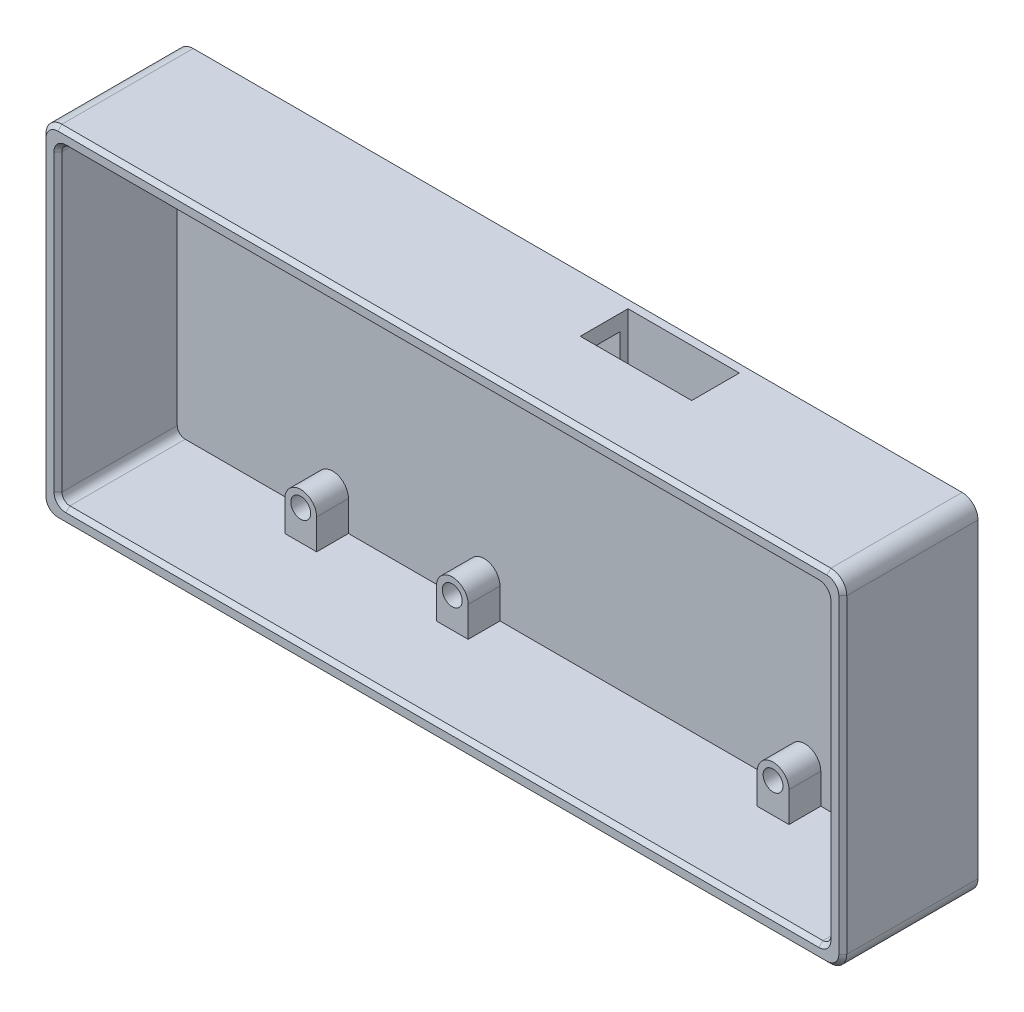
SolidWorks part; units mm, degrees
ref_plane "前视基准面" through (0, 0, 0) normal (0, 0, 1) x (1, 0, 0)
ref_plane "上视基准面" through (0, 0, 0) normal (0, 1, 0) x (1, 0, 0)
ref_plane "右视基准面" through (0, 0, 0) normal (1, 0, 0) x (0, 0, -1)
sketch "草图1" plane through (0, 0, 0) normal (0, 0, 1) x (1, 0, 0)
  line L2 (2.2254, 43.5224) -> (2.2254, 4.4743)
  line L3 (4.2254, 2.4743) -> (100.9001, 2.4743)
  line L4 (100.9001, 45.5224) -> (4.2254, 45.5224)
  line L5 (102.9001, 43.5224) -> (102.9001, 4.4743)
  line L6 (4.2254, 2.4743) -> (6.2254, 2.4743)
  line L7 (4.2252, 42.5233) -> (4.2259, 5.4743)
  line L8 (100.9003, 42.5234) -> (100.8996, 5.4743)
  line L9 (21.7509, 8.2734) -> (21.7509, 4.4743)
  line L10 (25.7509, 8.2727) -> (25.7509, 4.4743)
  line L11 (40.8008, 8.2727) -> (40.8008, 4.4743)
  line L12 (44.8008, 8.272) -> (44.8008, 4.4743)
  line L13 (81.1358, 8.2734) -> (81.1358, 4.4743)
  line L14 (85.1358, 8.2727) -> (85.1358, 4.4743)
  line L15 (21.7509, 39.7233) -> (21.7509, 43.5234)
  line L16 (25.7509, 39.7226) -> (25.7509, 43.5234)
  line L17 (40.8008, 39.7226) -> (40.8008, 43.5234)
  line L18 (44.8008, 39.7219) -> (44.8008, 43.5234)
  line L19 (81.1358, 39.7226) -> (81.1358, 43.5227)
  line L20 (85.1358, 39.7219) -> (85.1358, 43.5227)
  line L21 (5.2259, 4.4743) -> (21.7509, 4.4743)
  line L22 (21.7509, 4.4743) -> (25.7509, 4.4743)
  line L23 (25.7509, 4.4743) -> (40.8008, 4.4743)
  line L24 (40.8008, 4.4743) -> (44.8008, 4.4743)
  line L25 (44.8008, 4.4743) -> (81.1358, 4.4743)
  line L26 (81.1358, 4.4743) -> (85.1358, 4.4743)
  line L27 (85.1358, 4.4743) -> (99.8996, 4.4743)
  line L28 (99.9003, 43.5234) -> (85.1358, 43.5227)
  line L29 (85.1358, 43.5227) -> (81.1358, 43.5227)
  line L30 (81.1358, 43.5227) -> (44.8008, 43.5234)
  line L31 (44.8008, 43.5234) -> (40.8008, 43.5234)
  line L32 (40.8008, 43.5234) -> (25.7509, 43.5234)
  line L33 (25.7509, 43.5234) -> (21.7509, 43.5234)
  line L34 (21.7509, 43.5234) -> (5.2252, 43.5234)
  line L35 (71.9001, 43.5234) -> (61.9001, 43.5234)
  line L36 (71.9001, 43.5234) -> (71.9001, 33.5234)
  line L37 (71.9001, 33.5234) -> (61.9001, 33.5234)
  line L38 (61.9001, 33.5234) -> (61.9001, 43.5234)
  arc A0 (4.2254, 45.5224) -> (2.2254, 43.5224) centre (4.2254, 43.5224) ccw
  arc A1 (102.9001, 43.5224) -> (100.9001, 45.5224) centre (100.9001, 43.5224) ccw
  arc A2 (100.9001, 2.4743) -> (102.9001, 4.4743) centre (100.9001, 4.4743) ccw
  arc A3 (2.2254, 4.4743) -> (4.2254, 2.4743) centre (4.2254, 4.4743) ccw
  arc A4 (5.2252, 43.5234) -> (4.2252, 42.5233) centre (5.2252, 42.5234) ccw
  arc A5 (4.2259, 5.4743) -> (5.2259, 4.4743) centre (5.2259, 5.4743) ccw
  arc A6 (100.9003, 42.5234) -> (99.9003, 43.5234) centre (99.9003, 42.5234) ccw
  arc A7 (99.8996, 4.4743) -> (100.8996, 5.4743) centre (99.8996, 5.4743) ccw
  circle A8 centre (23.7509, 39.7226) radius 1.25
  circle A9 centre (42.8008, 39.7219) radius 1.25
  circle A10 centre (83.1358, 39.7219) radius 1.25
  circle A11 centre (23.7509, 8.2734) radius 1.25
  circle A12 centre (42.8008, 8.2727) radius 1.25
  circle A13 centre (83.1358, 8.2734) radius 1.25
  arc A14 (21.7509, 39.7233) -> (25.7509, 39.7226) centre (23.7509, 39.7226) ccw
  arc A15 (40.8008, 39.7226) -> (44.8008, 39.7219) centre (42.8008, 39.7219) ccw
  arc A16 (81.1358, 39.7226) -> (85.1358, 39.7219) centre (83.1358, 39.7219) ccw
  arc A17 (44.8008, 8.272) -> (40.8008, 8.2727) centre (42.8008, 8.2727) ccw
  arc A18 (25.7509, 8.2727) -> (21.7509, 8.2734) centre (23.7509, 8.2734) ccw
  arc A19 (85.1358, 8.2727) -> (81.1358, 8.2734) centre (83.1358, 8.2734) ccw
extrude "凸台-拉伸1" add sketch "草图1" along normal blind 2 contours L3 A2 L5 A1 L4 A0 L2 A3
sketch "草图2" plane through (0, 0, 2) normal (0, 0, 1) x (1, 0, 0)
  line L0 (61.9001, 33.5234) -> (61.9001, 43.5234) construction
  line L1 (71.9001, 33.5234) -> (61.9001, 33.5234) construction
  line L2 (71.9001, 43.5234) -> (71.9001, 33.5234) construction
  line L3 (61.9001, 33.5234) -> (61.9001, 43.5234)
  line L4 (71.9001, 33.5234) -> (61.9001, 33.5234)
  line L5 (71.9001, 43.5234) -> (71.9001, 33.5234)
  line L6 (61.9001, 43.5234) -> (71.9001, 43.5234)
extrude "切除-拉伸1" cut sketch "草图2" against normal blind 1
sketch "草图3" plane through (0, 0, 2) normal (0, 0, 1) x (1, 0, 0)
  line L0 (100.9001, 45.5224) -> (4.2254, 45.5224) construction
  line L1 (2.2254, 43.5224) -> (2.2254, 4.4743) construction
  line L2 (4.2254, 2.4743) -> (100.9001, 2.4743) construction
  line L3 (102.9001, 43.5224) -> (102.9001, 4.4743) construction
  line L4 (99.9003, 43.5234) -> (85.1358, 43.5227) construction
  line L5 (85.1358, 43.5227) -> (81.1358, 43.5227) construction
  line L6 (81.1358, 43.5227) -> (44.8008, 43.5234) construction
  line L7 (44.8008, 43.5234) -> (40.8008, 43.5234) construction
  line L8 (40.8008, 43.5234) -> (25.7509, 43.5234) construction
  line L9 (25.7509, 43.5234) -> (21.7509, 43.5234) construction
  line L10 (21.7509, 43.5234) -> (5.2252, 43.5234) construction
  line L11 (4.2252, 42.5233) -> (4.2259, 5.4743) construction
  line L12 (5.2259, 4.4743) -> (21.7509, 4.4743) construction
  line L13 (21.7509, 4.4743) -> (25.7509, 4.4743) construction
  line L14 (25.7509, 4.4743) -> (40.8008, 4.4743) construction
  line L15 (40.8008, 4.4743) -> (44.8008, 4.4743) construction
  line L16 (44.8008, 4.4743) -> (81.1358, 4.4743) construction
  line L17 (81.1358, 4.4743) -> (85.1358, 4.4743) construction
  line L18 (85.1358, 4.4743) -> (99.8996, 4.4743) construction
  line L19 (100.9003, 42.5234) -> (100.8996, 5.4743) construction
  line L20 (100.9001, 45.5224) -> (4.2254, 45.5224)
  line L21 (2.2254, 43.5224) -> (2.2254, 4.4743)
  line L22 (4.2254, 2.4743) -> (100.9001, 2.4743)
  line L23 (102.9001, 43.5224) -> (102.9001, 4.4743)
  line L24 (99.9003, 43.5234) -> (85.1358, 43.5227)
  line L25 (85.1358, 43.5227) -> (81.1358, 43.5227)
  line L26 (81.1358, 43.5227) -> (44.8008, 43.5234)
  line L27 (44.8008, 43.5234) -> (40.8008, 43.5234)
  line L28 (40.8008, 43.5234) -> (25.7509, 43.5234)
  line L29 (25.7509, 43.5234) -> (21.7509, 43.5234)
  line L30 (21.7509, 43.5234) -> (5.2252, 43.5234)
  line L31 (4.2252, 42.5233) -> (4.2259, 5.4743)
  line L32 (5.2259, 4.4743) -> (21.7509, 4.4743)
  line L33 (21.7509, 4.4743) -> (25.7509, 4.4743)
  line L34 (25.7509, 4.4743) -> (40.8008, 4.4743)
  line L35 (40.8008, 4.4743) -> (44.8008, 4.4743)
  line L36 (44.8008, 4.4743) -> (81.1358, 4.4743)
  line L37 (81.1358, 4.4743) -> (85.1358, 4.4743)
  line L38 (85.1358, 4.4743) -> (99.8996, 4.4743)
  line L39 (100.9003, 42.5234) -> (100.8996, 5.4743)
  arc A0 (4.2254, 45.5224) -> (2.2254, 43.5224) centre (4.2254, 43.5224) ccw construction
  arc A1 (2.2254, 4.4743) -> (4.2254, 2.4743) centre (4.2254, 4.4743) ccw construction
  arc A2 (100.9001, 2.4743) -> (102.9001, 4.4743) centre (100.9001, 4.4743) ccw construction
  arc A3 (102.9001, 43.5224) -> (100.9001, 45.5224) centre (100.9001, 43.5224) ccw construction
  arc A4 (99.8996, 4.4743) -> (100.8996, 5.4743) centre (99.8996, 5.4743) ccw construction
  arc A5 (100.9003, 42.5234) -> (99.9003, 43.5234) centre (99.9003, 42.5234) ccw construction
  arc A6 (5.2252, 43.5234) -> (4.2252, 42.5233) centre (5.2252, 42.5234) ccw construction
  arc A7 (4.2259, 5.4743) -> (5.2259, 4.4743) centre (5.2259, 5.4743) ccw construction
  arc A8 (4.2254, 45.5224) -> (2.2254, 43.5224) centre (4.2254, 43.5224) ccw
  arc A9 (2.2254, 4.4743) -> (4.2254, 2.4743) centre (4.2254, 4.4743) ccw
  arc A10 (100.9001, 2.4743) -> (102.9001, 4.4743) centre (100.9001, 4.4743) ccw
  arc A11 (102.9001, 43.5224) -> (100.9001, 45.5224) centre (100.9001, 43.5224) ccw
  arc A12 (99.8996, 4.4743) -> (100.8996, 5.4743) centre (99.8996, 5.4743) ccw
  arc A13 (100.9003, 42.5234) -> (99.9003, 43.5234) centre (99.9003, 42.5234) ccw
  arc A14 (5.2252, 43.5234) -> (4.2252, 42.5233) centre (5.2252, 42.5234) ccw
  arc A15 (4.2259, 5.4743) -> (5.2259, 4.4743) centre (5.2259, 5.4743) ccw
extrude "凸台-拉伸2" add sketch "草图3" along normal blind 15
sketch "草图4" plane through (0, 0, 2) normal (0, 0, 1) x (1, 0, 0)
  line L0 (21.7509, 39.7233) -> (21.7509, 43.5234) construction
  line L1 (25.7509, 43.5234) -> (21.7509, 43.5234) construction
  line L2 (25.7509, 39.7226) -> (25.7509, 43.5234) construction
  line L3 (40.8008, 39.7226) -> (40.8008, 43.5234) construction
  line L4 (44.8008, 43.5234) -> (40.8008, 43.5234) construction
  line L5 (44.8008, 39.7219) -> (44.8008, 43.5234) construction
  line L6 (81.1358, 39.7226) -> (81.1358, 43.5227) construction
  line L7 (85.1358, 43.5227) -> (81.1358, 43.5227) construction
  line L8 (85.1358, 39.7219) -> (85.1358, 43.5227) construction
  line L9 (21.7509, 8.2734) -> (21.7509, 4.4743) construction
  line L10 (21.7509, 4.4743) -> (25.7509, 4.4743) construction
  line L11 (25.7509, 8.2727) -> (25.7509, 4.4743) construction
  line L12 (40.8008, 8.2727) -> (40.8008, 4.4743) construction
  line L13 (40.8008, 4.4743) -> (44.8008, 4.4743) construction
  line L14 (44.8008, 8.272) -> (44.8008, 4.4743) construction
  line L15 (81.1358, 8.2734) -> (81.1358, 4.4743) construction
  line L16 (85.1358, 8.2727) -> (85.1358, 4.4743) construction
  line L17 (81.1358, 4.4743) -> (85.1358, 4.4743) construction
  line L18 (21.7509, 39.7233) -> (21.7509, 43.5234)
  line L19 (25.7509, 43.5234) -> (21.7509, 43.5234)
  line L20 (25.7509, 39.7226) -> (25.7509, 43.5234)
  line L21 (40.8008, 39.7226) -> (40.8008, 43.5234)
  line L22 (44.8008, 43.5234) -> (40.8008, 43.5234)
  line L23 (44.8008, 39.7219) -> (44.8008, 43.5234)
  line L24 (81.1358, 39.7226) -> (81.1358, 43.5227)
  line L25 (85.1358, 43.5227) -> (81.1358, 43.5227)
  line L26 (85.1358, 39.7219) -> (85.1358, 43.5227)
  line L27 (21.7509, 8.2734) -> (21.7509, 4.4743)
  line L28 (21.7509, 4.4743) -> (25.7509, 4.4743)
  line L29 (25.7509, 8.2727) -> (25.7509, 4.4743)
  line L30 (40.8008, 8.2727) -> (40.8008, 4.4743)
  line L31 (40.8008, 4.4743) -> (44.8008, 4.4743)
  line L32 (44.8008, 8.272) -> (44.8008, 4.4743)
  line L33 (81.1358, 8.2734) -> (81.1358, 4.4743)
  line L34 (85.1358, 8.2727) -> (85.1358, 4.4743)
  line L35 (81.1358, 4.4743) -> (85.1358, 4.4743)
  arc A0 (21.7509, 39.7233) -> (25.7509, 39.7226) centre (23.7509, 39.7226) ccw construction
  arc A1 (40.8008, 39.7226) -> (44.8008, 39.7219) centre (42.8008, 39.7219) ccw construction
  arc A2 (81.1358, 39.7226) -> (85.1358, 39.7219) centre (83.1358, 39.7219) ccw construction
  arc A3 (25.7509, 8.2727) -> (21.7509, 8.2734) centre (23.7509, 8.2734) ccw construction
  arc A4 (44.8008, 8.272) -> (40.8008, 8.2727) centre (42.8008, 8.2727) ccw construction
  arc A5 (85.1358, 8.2727) -> (81.1358, 8.2734) centre (83.1358, 8.2734) ccw construction
  arc A6 (21.7509, 39.7233) -> (25.7509, 39.7226) centre (23.7509, 39.7226) ccw
  arc A7 (40.8008, 39.7226) -> (44.8008, 39.7219) centre (42.8008, 39.7219) ccw
  arc A8 (81.1358, 39.7226) -> (85.1358, 39.7219) centre (83.1358, 39.7219) ccw
  arc A9 (25.7509, 8.2727) -> (21.7509, 8.2734) centre (23.7509, 8.2734) ccw
  arc A10 (44.8008, 8.272) -> (40.8008, 8.2727) centre (42.8008, 8.2727) ccw
  arc A11 (85.1358, 8.2727) -> (81.1358, 8.2734) centre (83.1358, 8.2734) ccw
extrude "凸台-拉伸3" add sketch "草图4" along normal blind 4
sketch "草图5" plane through (0, 0, 6) normal (0, 0, 1) x (1, 0, 0)
  point P0 (23.7509, 39.7226)
  point P1 (42.8008, 39.7219)
  point P3 (83.1358, 39.7219)
  point P5 (83.1358, 8.2734)
  point P7 (42.8008, 8.2727)
  point P9 (23.7509, 8.2734)
hole_wizard "大小mm 暗销孔2" positions "3D草图3" profile "草图8" hole size "Ø2.5" standard "GB"
sketch3d "3D草图3"
  point P0 (23.7509, 39.7226, 6)
  point P3 (42.8008, 39.7219, 6)
  point P6 (83.1358, 39.7219, 6)
  point P9 (83.1358, 8.2734, 6)
  point P12 (42.8008, 8.2727, 6)
  point P15 (23.7509, 8.2734, 6)
sketch "草图8" plane through (23.7509, 39.7226, 6) normal (1, 0, 0) x (0, -1, 0)
  line L0 (0, 0) -> (0, 4.7511)
  line L1 (0, 4.7511) -> (1.25, 4)
  line L2 (1.25, 4) -> (1.25, 0)
  line L5 (1.25, 0) -> (0, 0)
  line L10 (0, 4.7511) -> (-1.25, 4) construction
  line L11 (0, -6.35) -> (0, 107.95) construction
  dimension "孔直径" = 2.5
  dimension "孔深度" = 4
  dimension "导头角度" = 118
sketch "草图9" plane through (0, 45.5224, 0) normal (0, 1, 0) x (1, 0, 0)
  line L2 (59.9001, -1) -> (59.9001, -7)
  line L4 (59.9001, -7) -> (73.9001, -7)
  line L5 (59.9001, -1) -> (73.9001, -1)
  line L6 (73.9001, -1) -> (73.9001, -7)
extrude "切除-拉伸2" cut sketch "草图9" against normal blind 2
extrude "切除-拉伸3" cut sketch "草图9<2>" against normal blind 10
sketch "草图9<2>" plane through (0, 45.5224, 0) normal (0, 1, 0) x (1, 0, 0) same geometry as "草图9"
chamfer "倒角1" distance 0.5 angle 45 19 edges at (83.1358, 43.5227, 17) (62.9683, 43.523, 17) (25.013, 43.5234, 17) (4.5181, 43.2305, 17) (4.2255, 23.9988, 17) (4.5188, 4.7672, 17) (52.5627, 4.4743, 17) (100.6067, 4.7672, 17) (100.9, 23.9988, 17) (100.6074, 43.2305, 17) (92.518, 43.523, 17) (102.9001, 23.9983, 17) (102.3143, 3.0601, 17) (52.5628, 2.4743, 17) (2.8112, 3.0601, 17) (2.2254, 23.9983, 17) (2.8112, 44.9366, 17) (52.5628, 45.5224, 17) (102.3143, 44.9366, 17)
